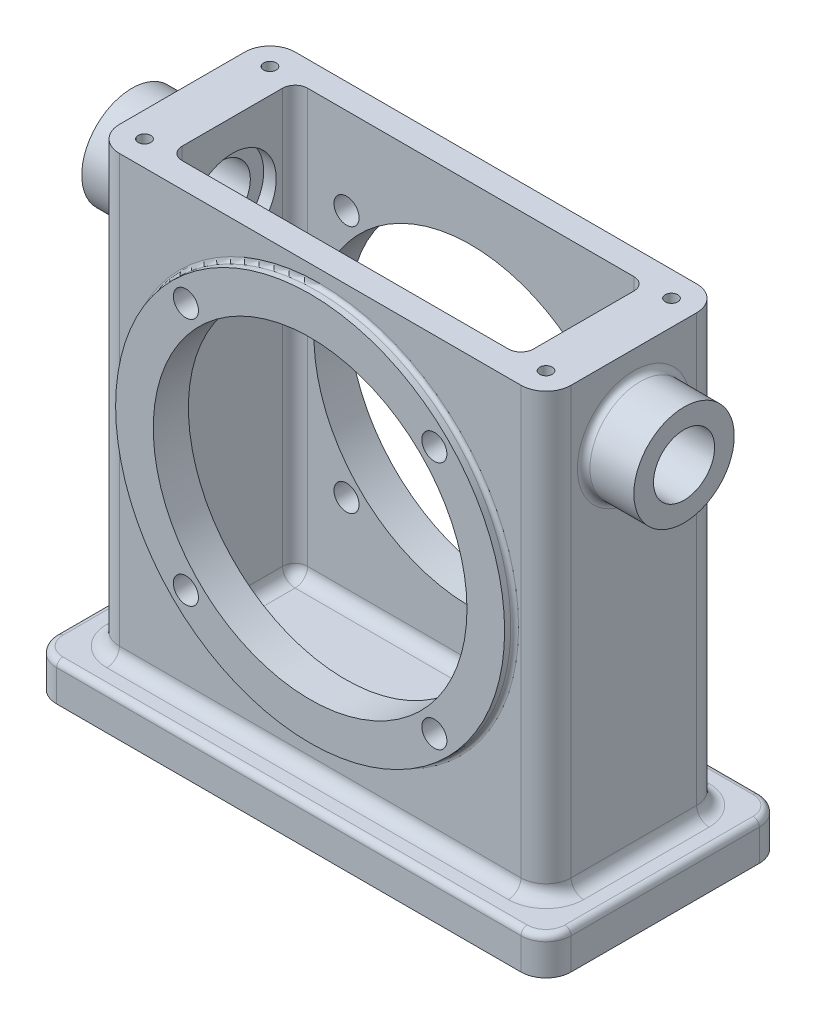
SolidWorks part; units mm, degrees
note: '?' marks a value the reader was unsure of.
ref_plane "Front" through (0, 0, 0) normal (0, 0, 1) x (1, 0, 0)
ref_plane "Top" through (0, 0, 0) normal (0, 1, 0) x (1, 0, 0)
ref_plane "Right" through (0, 0, 0) normal (1, 0, 0) x (0, 0, -1)
sketch "Sketch1" plane through (0, 0, 0) normal (0, 1, 0) x (1, 0, 0)
  line L0 (-65.0875, -30.1625) -> (65.0875, 30.1625) construction
  line L1 (-65.0875, -30.1625) -> (65.0875, -30.1625)
  line L2 (-65.0875, -30.1625) -> (-65.0875, 30.1625)
  line L3 (-65.0875, 30.1625) -> (65.0875, 30.1625)
  line L4 (65.0875, -30.1625) -> (65.0875, 30.1625)
  dimension "D1" = 130.175
  dimension "D2" = 60.325
extrude "Base-Extrude" add sketch "Sketch1" along normal blind 9.525
sketch "Sketch2" plane through (0, 9.525, 0) normal (0, 1, 0) x (-1, 0, 0)
  line L0 (57.15, 22.225) -> (-57.15, -22.225) construction
  line L1 (57.15, 22.225) -> (-57.15, 22.225)
  line L2 (57.15, 22.225) -> (57.15, -22.225)
  line L3 (57.15, -22.225) -> (-57.15, -22.225)
  line L4 (-57.15, 22.225) -> (-57.15, -22.225)
  dimension "D1" = 114.3
  dimension "D2" = 44.45
extrude "Boss-Extrude1" add sketch "Sketch2" along normal blind 111.125
fillet "Fillet1" radius 6.35 8 edges at (-57.15, 65.0875, -22.225) (-57.15, 65.0875, 22.225) (57.15, 65.0875, 22.225) (57.15, 65.0875, -22.225) (-65.0875, 4.7625, -30.1625) (65.0875, 4.7625, -30.1625) (65.0875, 4.7625, 30.1625) (-65.0875, 4.7625, 30.1625)
fillet "Fillet2" radius 1.5875 8 edges at (0, 9.525, 30.1625) (-65.0875, 9.525, 0) (65.0875, 9.525, 0) (0, 9.525, -30.1625) (-63.2276, 9.525, -28.3026) (63.2276, 9.525, 28.3026) (63.2276, 9.525, -28.3026) (-63.2276, 9.525, 28.3026)
fillet "Fillet3" radius 3.175 8 edges at (-57.15, 9.525, 0) (0, 9.525, -22.225) (57.15, 9.525, 0) (0, 9.525, 22.225) (-55.2901, 9.525, 20.3651) (-55.2901, 9.525, -20.3651) (55.2901, 9.525, 20.3651) (55.2901, 9.525, -20.3651)
sketch "Sketch3" plane through (0, 120.65, 0) normal (0, 1, 0) x (-1, 0, 0)
  line L2 (50.8, 15.875) -> (-50.8, 15.875)
  line L3 (41.275, 15.875) -> (-41.275, 15.875)
  line L5 (-50.8, -15.875) -> (50.8, -15.875)
  line L6 (-41.275, -15.875) -> (41.275, -15.875)
  line L8 (44.45, -15.875) -> (44.45, 15.875)
  line L9 (44.45, -12.7) -> (44.45, 12.7)
  line L11 (-44.45, 15.875) -> (-44.45, -15.875)
  line L12 (-44.45, 12.7) -> (-44.45, -12.7)
  arc A0 (-41.275, 15.875) -> (-44.45, 12.7) centre (-41.275, 12.7) ccw
  arc A1 (44.45, 12.7) -> (41.275, 15.875) centre (41.275, 12.7) ccw
  arc A2 (41.275, -15.875) -> (44.45, -12.7) centre (41.275, -12.7) ccw
  arc A3 (-44.45, -12.7) -> (-41.275, -15.875) centre (-41.275, -12.7) ccw
  dimension "D5" = 3.175
  dimension "D1" = 6.35
  dimension "D2" = 6.35
  dimension "D3" = 12.7
  dimension "D4" = 12.7
extrude "Cut-Extrude1" cut sketch "Sketch3" against normal blind 107.95
fillet "Fillet4" radius 3.175 8 edges at (43.5201, 12.7, 14.9451) (0, 12.7, 15.875) (-43.5201, 12.7, 14.9451) (-44.45, 12.7, 0) (-43.5201, 12.7, -14.9451) (0, 12.7, -15.875) (43.5201, 12.7, -14.9451) (44.45, 12.7, 0)
sketch "Sketch4" plane through (0, 0, 22.225) normal (0, 0, 1) x (1, 0, 0)
  line L0 (-50.8, 120.65) -> (50.8, 120.65) construction
  line L1 (0, -50) -> (0, 50) construction
  circle A0 centre (0, 67.31) radius 49.2125
  dimension "D1" = 98.425
  dimension "D2" = 53.34
extrude "Boss-Extrude2" add sketch "Sketch4" along normal blind 2.54
mirror "Mirror1" about plane through (0, 0, 0) normal (0, 0, 1) of "Boss-Extrude2"
sketch "Sketch5" plane through (0, 0, 24.765) normal (0, 0, 1) x (1, 0, 0)
  circle A0 centre (0, 67.31) radius 39.6875
  dimension "D1" = 79.375
extrude "Cut-Extrude2" cut sketch "Sketch5" against normal through all
fillet "Fillet5" radius 0.9906 2 edges at (-49.2125, 67.31, 22.225) (49.2125, 67.31, -22.225)
sketch "Sketch6" plane through (57.15, 0, 0) normal (1, 0, 0) x (0, 0, -1)
  line L0 (-23.8125, 0) -> (23.8125, 0) construction
  line L1 (0, 101.6) -> (0, 0) construction
  circle A0 centre (0, 101.6) radius 12.7
  dimension "D1" = 25.4
  dimension "D2" = 101.6
extrude "Boss-Extrude3" add sketch "Sketch6" along normal blind 12.7
sketch "Sketch7" plane through (44.45, 0, 0) normal (-1, 0, 0) x (0, 0, 1)
  circle A0 centre (0, 101.6) radius 7.7343
  dimension "D1" = 15.4686
extrude "Cut-Extrude3" cut sketch "Sketch7" against normal through all
sketch "Sketch8" plane through (44.45, 0, 0) normal (-1, 0, 0) x (0, 0, 1)
  circle A0 centre (0, 101.6) radius 11.1125
  dimension "D1" = 22.225
extrude "Cut-Extrude4" cut sketch "Sketch8" against normal blind 3.175
mirror "Mirror3" about plane through (0, 0, 0) normal (1, 0, 0) of "Cut-Extrude4", "Cut-Extrude3", "Boss-Extrude3"
fillet "Fillet6" radius 1.5875 2 edges at (57.15, 101.6, 12.7) (-57.15, 101.6, -12.7)
sketch "Sketch9" plane through (0, 0, 24.765) normal (0, 0, 1) x (1, 0, 0)
  line L0 (31.4309, 98.7409) -> (0, 67.31) construction
  line L1 (0, 67.31) -> (44.45, 67.31) construction
  circle A0 centre (0, 67.31) radius 44.45 construction
  circle A1 centre (31.4309, 98.7409) radius 3.175
  dimension "D1" = 88.9
  dimension "D2" = 6.35
  dimension "D3" = 45
extrude "Cut-Extrude5" cut sketch "Sketch9" against normal through all
ref_axis "CenterLargeHole" through (0, 67.31, -83.0711) along (0, 0, 1)?
pattern_circular "CirPattern1" count 4 over 360 about axis through (0, 67.31, 0) along (0, 0, 1) of "Cut-Extrude5"
sketch "Sketch10" plane through (0, 120.65, 0) normal (0, 1, 0) x (-1, 0, 0)
  line L0 (-41.275, -15.875) -> (41.275, -15.875) construction
  line L1 (41.275, 15.875) -> (-41.275, 15.875) construction
  line L2 (-57.15, 15.875) -> (-57.15, -15.875) construction
  circle A0 centre (-50.8, -15.875) radius 1.5875
  circle A1 centre (-50.8, 15.875) radius 1.5875
  dimension "D1" = 3.175
  dimension "D2" = 6.35
extrude "Cut-Extrude6" cut sketch "Sketch10" against normal blind 19.05
mirror "Mirror4" about plane through (0, 0, 0) normal (1, 0, 0) of "Cut-Extrude6"
sketch "Sketch11" plane through (0, 120.65, 0) normal (0, 1, 0) x (-1, 0, 0)
  line L0 (-69.85, 12.7) -> (-69.85, -12.7) construction
  line L1 (0, 0) -> (-69.85, 0)
  line L2 (0, 0) -> (0, 30.1625)
  line L3 (0, 30.1625) -> (-69.85, 30.1625)
  line L4 (-69.85, 0) -> (-69.85, 30.1625)
  line L5 (-58.7375, 30.1625) -> (58.7375, 30.1625) construction
extrude "section cut" [suppressed] cut sketch "Sketch11" against normal through all
